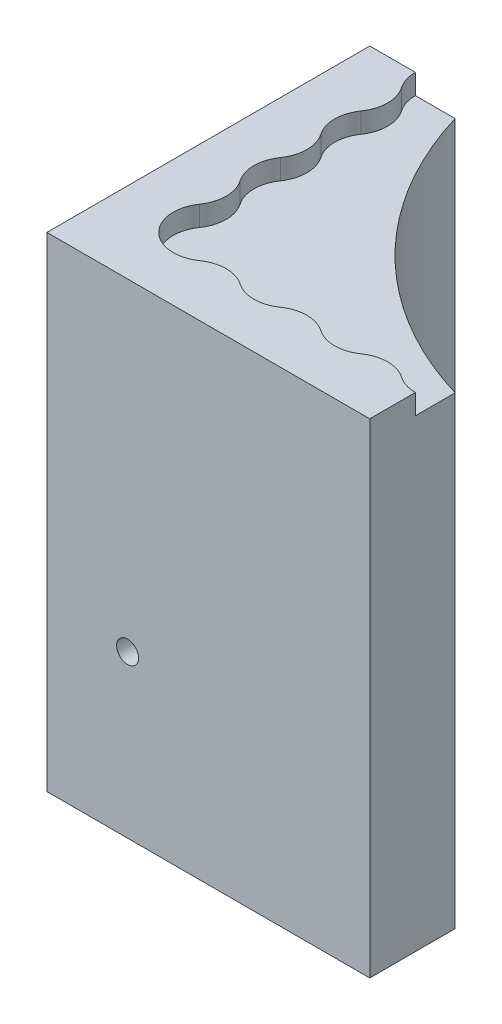
SolidWorks part; units mm, degrees
material "PET"
ref_plane "Front" through (0, 0, 0) normal (0, 0, 1) x (1, 0, 0)
ref_plane "Top" through (0, 0, 0) normal (0, 1, 0) x (1, 0, 0)
ref_plane "Right" through (0, 0, 0) normal (1, 0, 0) x (0, 0, -1)
sketch "Sketch1" plane through (0, 0, 0) normal (0, 1, 0) x (1, 0, 0)
  line L1 (0, 0) -> (50.8, 0)
  line L2 (0, 0) -> (0, 50.8)
  line L3 (0, 50.8) -> (50.8, 50.8)
  line L4 (50.8, 0) -> (50.8, 50.8)
  circle A0 centre (66.675, 66.675) radius 55.5625 construction
  dimension "D1" = 66.675
  dimension "D2" = 111.125
  dimension "D3" = 66.675
  dimension "D4" = 50.8
extrude "Boss-Extrude1" add sketch "Sketch1" along normal blind 76.2
sketch "Sketch2" plane through (0, 76.2, 0) normal (0, 1, 0) x (1, 0, 0)
  line L8 (129.2582, 124.9484) -> (133.499, 78.5045) construction
  line L9 (85.192, 137.4546) -> (125.4736, 129.1805) construction
  line L10 (129.2582, 124.9484) -> (133.499, 78.5045) construction
  line L11 (85.192, 137.4546) -> (125.4736, 129.1805) construction
  line L12 (130.017, 125.0177) -> (134.2578, 78.5738)
  line L13 (85.3453, 138.201) -> (125.6269, 129.9269)
  arc A0 (8.7916, 91.6214) -> (8.7916, 98.8786) centre (3.5805, 95.25) ccw construction
  arc A1 (8.7916, 91.6214) -> (8.7916, 86.1786) centre (12.7, 88.9) ccw construction
  arc A2 (8.7916, 78.9214) -> (8.7916, 86.1786) centre (3.5805, 82.55) ccw construction
  arc A3 (8.7916, 78.9214) -> (8.7796, 73.4959) centre (12.7, 76.2) ccw construction
  arc A4 (8.8014, 66.3169) -> (8.7796, 73.4959) centre (3.5524, 69.8905) ccw construction
  arc A5 (8.8014, 66.3169) -> (8.8053, 60.7032) centre (12.9199, 63.5129) ccw construction
  arc A6 (8.7834, 53.5096) -> (8.8053, 60.7032) centre (3.5613, 57.1223) ccw construction
  arc A7 (8.7834, 53.5096) -> (8.7916, 48.0786) centre (12.7, 50.8) ccw construction
  arc A8 (8.7916, 40.8214) -> (8.7916, 48.0786) centre (3.5805, 44.45) ccw construction
  arc A9 (8.7916, 40.8214) -> (8.7916, 35.3786) centre (12.7, 38.1) ccw construction
  arc A10 (8.7916, 28.1214) -> (8.7916, 35.3786) centre (3.5805, 31.75) ccw construction
  arc A11 (8.7916, 28.1214) -> (8.7916, 22.6786) centre (12.7, 25.4) ccw construction
  arc A12 (8.7916, 15.4214) -> (8.7916, 22.6786) centre (3.5805, 19.05) ccw construction
  arc A13 (8.7916, 15.4214) -> (15.4214, 8.7916) centre (12.7, 12.7) ccw construction
  arc A14 (22.6786, 8.7916) -> (15.4214, 8.7916) centre (19.05, 3.5805) ccw construction
  arc A15 (22.6786, 8.7916) -> (28.1214, 8.7916) centre (25.4, 12.7) ccw construction
  arc A16 (35.3786, 8.7916) -> (28.1214, 8.7916) centre (31.75, 3.5805) ccw construction
  arc A17 (35.3786, 8.7916) -> (40.8214, 8.7916) centre (38.1, 12.7) ccw construction
  arc A18 (48.0786, 8.7916) -> (40.8214, 8.7916) centre (44.45, 3.5805) ccw construction
  arc A19 (48.0786, 8.7916) -> (53.5096, 8.7834) centre (50.8, 12.7) ccw construction
  arc A20 (60.7032, 8.8053) -> (53.5096, 8.7834) centre (57.1223, 3.5613) ccw construction
  arc A21 (60.7032, 8.8053) -> (66.3169, 8.8014) centre (63.5129, 12.9199) ccw construction
  arc A22 (73.4959, 8.7796) -> (66.3169, 8.8014) centre (69.8905, 3.5524) ccw construction
  arc A23 (73.4959, 8.7796) -> (78.9214, 8.7916) centre (76.2, 12.7) ccw construction
  arc A24 (86.1786, 8.7916) -> (78.9214, 8.7916) centre (82.55, 3.5805) ccw construction
  arc A25 (86.1786, 8.7916) -> (91.6214, 8.7916) centre (88.9, 12.7) ccw construction
  arc A26 (98.8786, 8.7916) -> (91.6214, 8.7916) centre (95.25, 3.5805) ccw construction
  arc A27 (98.8786, 8.7916) -> (105.5642, 15.3394) centre (101.6, 12.7) ccw construction
  arc A28 (113.5841, 27.9306) -> (105.5642, 15.3394) centre (112.3572, 19.8624) ccw construction
  arc A29 (113.5841, 27.9306) -> (119.0625, 32.6538) centre (114.3, 32.639) ccw construction
  arc A30 (119.9168, 35.8549) -> (119.0625, 32.6538) centre (125.4124, 32.6736) ccw construction
  arc A31 (119.9168, 35.8549) -> (127.8227, 59.9277) centre (66.675, 66.675) ccw construction
  arc A32 (132.1466, 72.652) -> (127.8227, 59.9277) centre (158.75, 56.515) ccw construction
  arc A33 (132.1466, 72.652) -> (133.499, 78.5045) centre (123.9376, 77.6314) ccw construction
  arc A34 (129.2582, 124.9484) -> (125.4736, 129.1805) centre (124.5154, 124.5154) ccw construction
  arc A35 (85.192, 137.4546) -> (76.9535, 135.2891) centre (83.2602, 128.0498) ccw construction
  arc A36 (59.9277, 127.8227) -> (76.9535, 135.2891) centre (56.515, 158.75) ccw construction
  arc A37 (59.9277, 127.8227) -> (35.8549, 119.9168) centre (66.675, 66.675) ccw construction
  arc A38 (32.6538, 119.0625) -> (35.8549, 119.9168) centre (32.6736, 125.4124) ccw construction
  arc A39 (32.6538, 119.0625) -> (27.9306, 113.5841) centre (32.639, 114.3) ccw construction
  arc A40 (15.3394, 105.5642) -> (27.9306, 113.5841) centre (19.8624, 112.3572) ccw construction
  arc A41 (15.3394, 105.5642) -> (8.7916, 98.8786) centre (12.7, 101.6) ccw construction
  arc A42 (8.7916, 91.6214) -> (8.7916, 98.8786) centre (3.5805, 95.25) ccw construction
  arc A43 (8.7916, 91.6214) -> (8.7916, 86.1786) centre (12.7, 88.9) ccw construction
  arc A44 (8.7916, 78.9214) -> (8.7916, 86.1786) centre (3.5805, 82.55) ccw construction
  arc A45 (8.7916, 78.9214) -> (8.7796, 73.4959) centre (12.7, 76.2) ccw construction
  arc A46 (8.8014, 66.3169) -> (8.7796, 73.4959) centre (3.5524, 69.8905) ccw construction
  arc A47 (8.8014, 66.3169) -> (8.8053, 60.7032) centre (12.9199, 63.5129) ccw construction
  arc A48 (8.7834, 53.5096) -> (8.8053, 60.7032) centre (3.5613, 57.1223) ccw construction
  arc A49 (8.7834, 53.5096) -> (8.7916, 48.0786) centre (12.7, 50.8) ccw construction
  arc A50 (8.7916, 40.8214) -> (8.7916, 48.0786) centre (3.5805, 44.45) ccw construction
  arc A51 (8.7916, 40.8214) -> (8.7916, 35.3786) centre (12.7, 38.1) ccw construction
  arc A52 (8.7916, 28.1214) -> (8.7916, 35.3786) centre (3.5805, 31.75) ccw construction
  arc A53 (8.7916, 28.1214) -> (8.7916, 22.6786) centre (12.7, 25.4) ccw construction
  arc A54 (8.7916, 15.4214) -> (8.7916, 22.6786) centre (3.5805, 19.05) ccw construction
  arc A55 (8.7916, 15.4214) -> (15.4214, 8.7916) centre (12.7, 12.7) ccw construction
  arc A56 (22.6786, 8.7916) -> (15.4214, 8.7916) centre (19.05, 3.5805) ccw construction
  arc A57 (22.6786, 8.7916) -> (28.1214, 8.7916) centre (25.4, 12.7) ccw construction
  arc A58 (35.3786, 8.7916) -> (28.1214, 8.7916) centre (31.75, 3.5805) ccw construction
  arc A59 (35.3786, 8.7916) -> (40.8214, 8.7916) centre (38.1, 12.7) ccw construction
  arc A60 (48.0786, 8.7916) -> (40.8214, 8.7916) centre (44.45, 3.5805) ccw construction
  arc A61 (48.0786, 8.7916) -> (53.5096, 8.7834) centre (50.8, 12.7) ccw construction
  arc A62 (60.7032, 8.8053) -> (53.5096, 8.7834) centre (57.1223, 3.5613) ccw construction
  arc A63 (60.7032, 8.8053) -> (66.3169, 8.8014) centre (63.5129, 12.9199) ccw construction
  arc A64 (73.4959, 8.7796) -> (66.3169, 8.8014) centre (69.8905, 3.5524) ccw construction
  arc A65 (73.4959, 8.7796) -> (78.9214, 8.7916) centre (76.2, 12.7) ccw construction
  arc A66 (86.1786, 8.7916) -> (78.9214, 8.7916) centre (82.55, 3.5805) ccw construction
  arc A67 (86.1786, 8.7916) -> (91.6214, 8.7916) centre (88.9, 12.7) ccw construction
  arc A68 (98.8786, 8.7916) -> (91.6214, 8.7916) centre (95.25, 3.5805) ccw construction
  arc A69 (98.8786, 8.7916) -> (105.5642, 15.3394) centre (101.6, 12.7) ccw construction
  arc A70 (113.5841, 27.9306) -> (105.5642, 15.3394) centre (112.3572, 19.8624) ccw construction
  arc A71 (113.5841, 27.9306) -> (119.0625, 32.6538) centre (114.3, 32.639) ccw construction
  arc A72 (119.9168, 35.8549) -> (119.0625, 32.6538) centre (125.4124, 32.6736) ccw construction
  arc A73 (119.9168, 35.8549) -> (127.8227, 59.9277) centre (66.675, 66.675) ccw construction
  arc A74 (132.1466, 72.652) -> (127.8227, 59.9277) centre (158.75, 56.515) ccw construction
  arc A75 (132.1466, 72.652) -> (133.499, 78.5045) centre (123.9376, 77.6314) ccw construction
  arc A76 (129.2582, 124.9484) -> (125.4736, 129.1805) centre (124.5154, 124.5154) ccw construction
  arc A77 (85.192, 137.4546) -> (76.9535, 135.2891) centre (83.2602, 128.0498) ccw construction
  arc A78 (59.9277, 127.8227) -> (76.9535, 135.2891) centre (56.515, 158.75) ccw construction
  arc A79 (59.9277, 127.8227) -> (35.8549, 119.9168) centre (66.675, 66.675) ccw construction
  arc A80 (32.6538, 119.0625) -> (35.8549, 119.9168) centre (32.6736, 125.4124) ccw construction
  arc A81 (32.6538, 119.0625) -> (27.9306, 113.5841) centre (32.639, 114.3) ccw construction
  arc A82 (15.3394, 105.5642) -> (27.9306, 113.5841) centre (19.8624, 112.3572) ccw construction
  arc A83 (15.3394, 105.5642) -> (8.7916, 98.8786) centre (12.7, 101.6) ccw construction
  arc A84 (132.7981, 72.2568) -> (134.2578, 78.5738) centre (123.9376, 77.6314) ccw
  arc A85 (132.7981, 72.2568) -> (128.5801, 59.8441) centre (158.75, 56.515) ccw
  arc A86 (120.5763, 35.4731) -> (128.5801, 59.8441) centre (66.675, 66.675) ccw
  arc A87 (120.5763, 35.4731) -> (119.8245, 32.6562) centre (125.4124, 32.6736) ccw
  arc A88 (113.4695, 27.1773) -> (119.8245, 32.6562) centre (114.3, 32.639) ccw
  arc A89 (113.4695, 27.1773) -> (106.1985, 15.7617) centre (112.3572, 19.8624) ccw
  arc A90 (98.4431, 8.1663) -> (106.1985, 15.7617) centre (101.6, 12.7) ccw
  arc A91 (98.4431, 8.1663) -> (92.0569, 8.1663) centre (95.25, 3.5805) ccw
  arc A92 (85.7431, 8.1663) -> (92.0569, 8.1663) centre (88.9, 12.7) ccw
  arc A93 (85.7431, 8.1663) -> (79.3569, 8.1663) centre (82.55, 3.5805) ccw
  arc A94 (73.0633, 8.1523) -> (79.3569, 8.1663) centre (76.2, 12.7) ccw
  arc A95 (73.0633, 8.1523) -> (66.7457, 8.1715) centre (69.8905, 3.5524) ccw
  arc A96 (60.2735, 8.176) -> (66.7457, 8.1715) centre (63.5129, 12.9199) ccw
  arc A97 (60.2735, 8.176) -> (53.9431, 8.1568) centre (57.1223, 3.5613) ccw
  arc A98 (47.6431, 8.1663) -> (53.9431, 8.1568) centre (50.8, 12.7) ccw
  arc A99 (47.6431, 8.1663) -> (41.2569, 8.1663) centre (44.45, 3.5805) ccw
  arc A100 (34.9431, 8.1663) -> (41.2569, 8.1663) centre (38.1, 12.7) ccw
  arc A101 (34.9431, 8.1663) -> (28.5569, 8.1663) centre (31.75, 3.5805) ccw
  arc A102 (22.2431, 8.1663) -> (28.5569, 8.1663) centre (25.4, 12.7) ccw
  arc A103 (22.2431, 8.1663) -> (15.8569, 8.1663) centre (19.05, 3.5805) ccw
  arc A104 (8.1663, 15.8569) -> (15.8569, 8.1663) centre (12.7, 12.7) ccw
  arc A105 (8.1663, 15.8569) -> (8.1663, 22.2431) centre (3.5805, 19.05) ccw
  arc A106 (8.1663, 28.5569) -> (8.1663, 22.2431) centre (12.7, 25.4) ccw
  arc A107 (8.1663, 28.5569) -> (8.1663, 34.9431) centre (3.5805, 31.75) ccw
  arc A108 (8.1663, 41.2569) -> (8.1663, 34.9431) centre (12.7, 38.1) ccw
  arc A109 (8.1663, 41.2569) -> (8.1663, 47.6431) centre (3.5805, 44.45) ccw
  arc A110 (8.1568, 53.9431) -> (8.1663, 47.6431) centre (12.7, 50.8) ccw
  arc A111 (8.1568, 53.9431) -> (8.176, 60.2735) centre (3.5613, 57.1223) ccw
  arc A112 (8.1715, 66.7457) -> (8.176, 60.2735) centre (12.9199, 63.5129) ccw
  arc A113 (8.1715, 66.7457) -> (8.1523, 73.0633) centre (3.5524, 69.8905) ccw
  arc A114 (8.1663, 79.3569) -> (8.1523, 73.0633) centre (12.7, 76.2) ccw
  arc A115 (8.1663, 79.3569) -> (8.1663, 85.7431) centre (3.5805, 82.55) ccw
  arc A116 (8.1663, 92.0569) -> (8.1663, 85.7431) centre (12.7, 88.9) ccw
  arc A117 (8.1663, 92.0569) -> (8.1663, 98.4431) centre (3.5805, 95.25) ccw
  arc A118 (15.7617, 106.1985) -> (8.1663, 98.4431) centre (12.7, 101.6) ccw
  arc A119 (15.7617, 106.1985) -> (27.1773, 113.4695) centre (19.8624, 112.3572) ccw
  arc A120 (32.6562, 119.8245) -> (27.1773, 113.4695) centre (32.639, 114.3) ccw
  arc A121 (32.6562, 119.8245) -> (35.4731, 120.5763) centre (32.6736, 125.4124) ccw
  arc A122 (59.8441, 128.5801) -> (35.4731, 120.5763) centre (66.675, 66.675) ccw
  arc A123 (59.8441, 128.5801) -> (76.4529, 135.8637) centre (56.515, 158.75) ccw
  arc A124 (85.3453, 138.201) -> (76.4529, 135.8637) centre (83.2602, 128.0498) ccw
  arc A125 (130.017, 125.0177) -> (125.6269, 129.9269) centre (124.5154, 124.5154) ccw
  dimension "D1" = 0.762
extrude "Cut-Extrude1" cut sketch "Sketch2" against normal blind 3.175
sketch "Sketch3" plane through (0, 76.2, 0) normal (0, 1, 0) x (1, 0, 0)
  circle A0 centre (66.675, 66.675) radius 55.5625 construction
  circle A1 centre (66.675, 66.675) radius 55.5625
extrude "Cut-Extrude2" cut sketch "Sketch3" against normal through all
hole_wizard "#8-32 Tapped Hole1" positions "Sketch4" profile "Sketch5" tap size "#8-32" standard "ANSI Inch"
sketch "Sketch4" plane through (393.7, -15.875, 0) normal (0, 0, 1) x (1, 0, 0)
  point P30 (-381, 41.275)
sketch "Sketch5" plane through (12.7, 25.4, 0) normal (1, 0, 0) x (0, -1, 0)
  line L0 (0, 0) -> (0, 11.7464)
  line L1 (0, 11.7464) -> (1.7272, 10.7086)
  line L2 (1.7272, 10.7086) -> (1.7272, 0)
  line L3 (1.7272, 0) -> (0, 0)
  line L4 (0, 11.7464) -> (-1.7272, 10.7086) construction
  line L5 (0, -6.35) -> (0, 107.95) construction
  dimension "Tap Drill Dia." = 3.4544
  dimension "Tap Drill Depth" = 10.7086
  dimension "Drill Angle" = 118
hole_wizard "#8-32 Tapped Hole2" positions "Sketch6" profile "Sketch7" tap size "#8-32" standard "ANSI Inch"
sketch "Sketch6" plane through (0, -15.875, -393.7) normal (-1, 0, 0) x (0, 0, 1)
  point P36 (381, 41.275)
sketch "Sketch7" plane through (0, 25.4, -12.7) normal (0, 1, 0) x (0, 0, 1)
  line L0 (0, 0) -> (0, 11.7464)
  line L1 (0, 11.7464) -> (1.7272, 10.7086)
  line L2 (1.7272, 10.7086) -> (1.7272, 0)
  line L3 (1.7272, 0) -> (0, 0)
  line L4 (0, 11.7464) -> (-1.7272, 10.7086) construction
  line L5 (0, -6.35) -> (0, 107.95) construction
  dimension "Tap Drill Dia." = 3.4544
  dimension "Tap Drill Depth" = 10.7086
  dimension "Drill Angle" = 118
